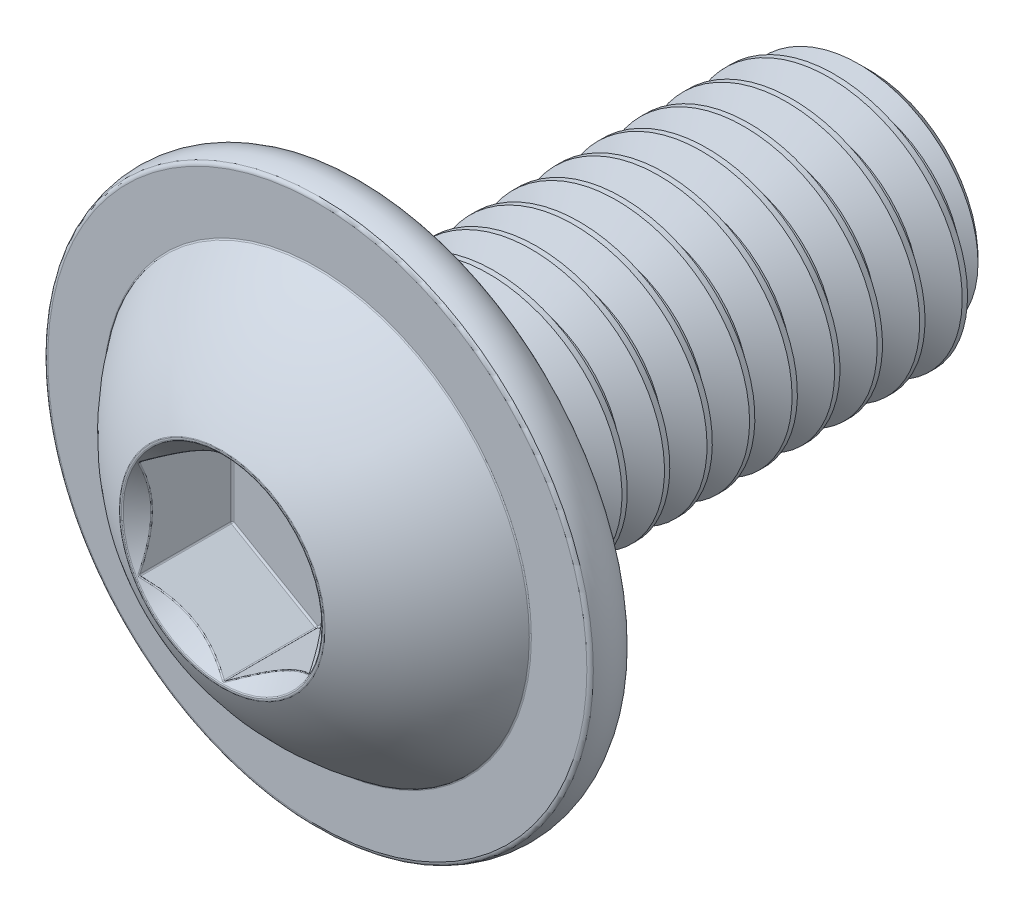
SolidWorks part; units mm, degrees
ref_plane "Front Plane" through (0, 0, 0) normal (0, 0, 1) x (1, 0, 0)
ref_plane "Top Plane" through (0, 0, 0) normal (0, 1, 0) x (1, 0, 0)
ref_plane "Right Plane" through (0, 0, 0) normal (1, 0, 0) x (0, 0, -1)
sketch "Sketch1" plane through (0, 0, 0) normal (1, 0, 0) x (0, 0, -1)
  line L0 (-6.0452, 0) -> (6.0452, 0) construction
  line L1 (6.0452, 0) -> (6.0452, 2.413)
  line L2 (6.0452, 2.413) -> (-3.4798, 2.413)
  line L3 (-3.4798, 2.413) -> (-3.4798, 0)
  line L4 (6.0452, 0) -> (6.839, 0) construction
  line L5 (6.0452, 2.0161) -> (5.6483, 2.413)
  line L6 (-3.4798, 2.413) -> (-3.4798, 5.1594)
  line L7 (-3.4798, 5.1594) -> (-4.2672, 5.1594)
  line L8 (-4.2672, 5.1594) -> (-4.2672, 4.372)
  line L9 (-6.0452, 0) -> (-6.0452, 1.8331)
  line L10 (-4.2672, 4.372) -> (-4.2672, 3.5846) construction
  line L11 (-6.0452, 1.8331) -> (-7.6327, 0.9165)
  line L12 (-7.6327, 0.9165) -> (-7.6327, -0.9165)
  line L13 (-7.6327, -0.9165) -> (-6.0452, -1.8331)
  line L14 (-6.0452, -1.8331) -> (-4.4577, -0.9165)
  line L15 (-4.4577, -0.9165) -> (-4.4577, 0.9165)
  line L16 (-4.4577, 0.9165) -> (-6.0452, 1.8331)
  line L17 (-3.4798, 2.794) -> (-3.4798, -2.794) construction
  circle A1 centre (-6.0452, 0) radius 1.5875 construction
  arc A3 (-4.2672, 3.9783) -> (-6.0452, 1.9125) centre (-1.1879, -0.4701) ccw
  point P2 (0, 0)
  point P10 (4.8546, -2.413)
  point P16 (6.0452, -2.413)
  point P17 (-3.4798, 5.1594)
  point P18 (6.0452, 2.413)
  point P20 (4.8546, 2.413)
  dimension "Head Radii" = 5.4102
  dimension "D1" = 45
  dimension "D3" = 0.3969
  dimension "D4" = 1.1906
  dimension "D2" = 0.0794
sketch "Sketch3" plane through (0, 0, 0) normal (1, 0, 0) x (0, 0, -1)
  line L0 (-3.4798, 2.413) -> (-3.4798, 5.1594) construction
  line L1 (-3.4798, 5.1594) -> (-4.2672, 5.1594) construction
  line L2 (-3.4798, 5.1594) -> (-3.4798, 2.794) construction
  line L3 (-6.0452, 0) -> (-6.0452, 1.8331) construction
  line L4 (-3.4798, 2.413) -> (-3.4798, 5.1594) construction
  line L5 (-3.4798, 5.1594) -> (-4.2672, 5.1594) construction
  line L7 (-6.0452, 0) -> (-6.0452, 1.9125)
  line L8 (-3.4798, 2.413) -> (5.6483, 2.413) construction
  line L9 (5.6483, 2.413) -> (6.0452, 2.0161)
  line L10 (6.0452, 2.0161) -> (6.0452, 0)
  line L11 (6.0452, 0) -> (-6.0452, 0)
  line L12 (-4.2672, 3.9783) -> (-4.2672, 5.1594) construction
  line L13 (-3.0988, 2.413) -> (5.6483, 2.413)
  line L14 (-4.2672, 3.9783) -> (-4.2672, 5.0806)
  line L15 (-3.4798, 2.794) -> (-3.4798, 5.0019)
  line L16 (-4.2672, 5.1594) -> (-4.2672, 5.0019) construction
  arc A0 (-4.2672, 3.9783) -> (-6.0452, 1.9125) centre (-1.1879, -0.4701) ccw construction
  arc A2 (-4.2672, 5.0806) -> (-3.4798, 5.0019) centre (-3.9355, 4.4213) cw
  arc A4 (-4.2672, 3.9783) -> (-6.0452, 1.9125) centre (-1.1879, -0.4701) ccw
  arc A5 (-3.4798, 2.794) -> (-3.0988, 2.413) centre (-3.0988, 2.794) ccw
  dimension "D1" = 0.1575
revolve "Revolve1" add sketch "Sketch3" angle 360 about L11
sketch "Sketch4" plane through (0, 0, 6.0452) normal (0, 0, 1) x (1, 0, 0)
  line L13 (0, 1.8331) -> (-1.5875, 0.9165)
  line L14 (-1.5875, 0.9165) -> (-1.5875, -0.9165)
  line L15 (-1.5875, -0.9165) -> (0, -1.8331)
  line L16 (0, -1.8331) -> (1.5875, -0.9165)
  line L17 (1.5875, -0.9165) -> (1.5875, 0.9165)
  line L18 (1.5875, 0.9165) -> (0, 1.8331)
  circle A0 centre (0, 0) radius 1.5875 construction
  dimension "D1" = 3.175
extrude "Cut-Extrude1" cut sketch "Sketch4" against normal up to surface (1.778 mm away) up to face at (-3.9783, 0, 4.2672)
sketch "Sketch5" plane through (0, 0, 6.0452) normal (0, 0, 1) x (1, 0, 0)
  line L0 (0, 1.8331) -> (0, 1.8648) construction
  circle A1 centre (0, 0) radius 1.8648
  dimension "D1" = 0.0318
extrude "Cut-Extrude2" cut sketch "Sketch5" against normal up to surface (1.778 mm away) draft 45 up to face at (0, 0, 4.2672)
fillet "Fillet3" radius 0.0318 21 edges at (-0.8935, -1.3172, 5.772) (0.694, -1.4324, 5.772) (0, -1.8331, 5.1403) (1.5875, -0.0193, 5.768) (1.5875, -0.9165, 5.1403) (0.8935, 1.3172, 5.772) (1.5875, 0.9165, 5.1403) (1.5875, 0, 4.2672) (0.7937, -1.3748, 4.2672) (-0.7937, -1.3748, 4.2672) (0.7937, 1.3748, 4.2672) (-1.5875, 0, 4.2672) (-1.5875, -0.9165, 5.1403) (-1.5875, -0.0193, 5.768) (-0.7938, 1.3748, 4.2672) (-1.5875, 0.9165, 5.1403) (-0.694, 1.4324, 5.772) (0, 1.8331, 5.1403) (-1.9125, 0, 6.0452) (1.8648, 0, 6.0452) (-3.9783, 0, 4.2672)
fillet "Fillet4" radius 0.0787 2 edges at (-5.0019, 0, 3.4798) (-5.0806, 0, 4.2672)
sketch "Reference Sketch1" plane through (0, 0, 0) normal (0, 0, 1) x (1, 0, 0)
  circle A0 centre (0, 0) radius 5.1594 construction
ref_plane "Plane1" through (0, 0, 3.0988) normal (0, 0, 1) x (1, 0, 0)
split "Split1" trim tools "Plane1" bodies to split 106 resulting bodies 108 111
sketch "Sketch6" plane through (0, 0, -6.0452) normal (0, 0, -1) x (-1, 0, 0)
  circle A1 centre (0, 0) radius 2.413
curve "Helix/Spiral1" pitch 0.7937 height 10.7156 radius 2.413 centre (0, 0, -6.0452) axis (0, 0, 1) start towards (0, 1, 0)
sketch "Sketch7" plane through (0, 0, 0) normal (1, 0, 0) x (0, 0, -1)
  line L0 (5.9956, 2.4989) -> (6.3925, 1.8115) construction
  line L1 (6.3925, 1.8115) -> (6.7893, 2.4989) construction
  line L2 (6.7893, 2.4989) -> (5.9956, 2.4989) construction
  line L3 (6.0204, 2.456) -> (6.7645, 2.456)
  line L4 (6.7645, 2.456) -> (6.4421, 1.8974)
  line L5 (6.4421, 1.8974) -> (6.3429, 1.8974)
  line L6 (6.3429, 1.8974) -> (6.0204, 2.456)
  line L7 (6.3925, 1.8974) -> (6.3925, 1.8115) construction
  line L8 (6.0452, 2.413) -> (6.7397, 2.413) construction
  line L9 (6.3925, 2.4989) -> (6.3925, 2.413) construction
  point P12 (6.3925, 2.456)
  dimension "D1" = 0.7937
  dimension "D2" = 0.0992
sweep "Cut-Sweep1" cut profiles "Sketch7" path "Helix/Spiral1" align with end faces yes
sketch "Sketch8" plane through (0, 0, 3.0988) normal (0, 0, 1) x (1, 0, 0)
  circle A2 centre (0, 0) radius 2.413
  circle A3 centre (0, 0) radius 2.413
  dimension "D1" = 0
extrude "Boss-Extrude1" add sketch "Sketch8" against normal through all draft 45
equation "\"D3@Sketch1\"=0.5*\"Pitch@Sketch1\""
equation "\"D4@Helix/Spiral1\"=\"Pitch@Sketch1\""
equation "\"D3@Helix/Spiral1\"=\"Pitch@Sketch1\"*1.5+\"Length@Sketch1\""
equation "\"D1@Sketch7\"=\"Pitch@Sketch1\""
equation "\"D2@Sketch7\"=\"D1@Sketch7\"/8"
equation "\"D4@Sketch1\"=\"Pitch@Sketch1\"*1.5"
equation "\"D1@Sketch4\"=\"Drive Size@Sketch1\""
equation "\"D1@Sketch5\"=\"Drive Size@Sketch1\"*0.01"
equation "\"D2@Sketch1\"=\"Drive Size@Sketch1\"*0.025"
equation "\"D1@Fillet3\"=\"Drive Size@Sketch1\"*0.01"
equation "\"D1@Fillet4\"=(\"Head Height@Sketch1\"-\"Hex Key Engagement@Sketch1\")*0.1"
equation "\"D1@Sketch3\"=(\"Head Height@Sketch1\"-\"Hex Key Engagement@Sketch1\")*0.2"
